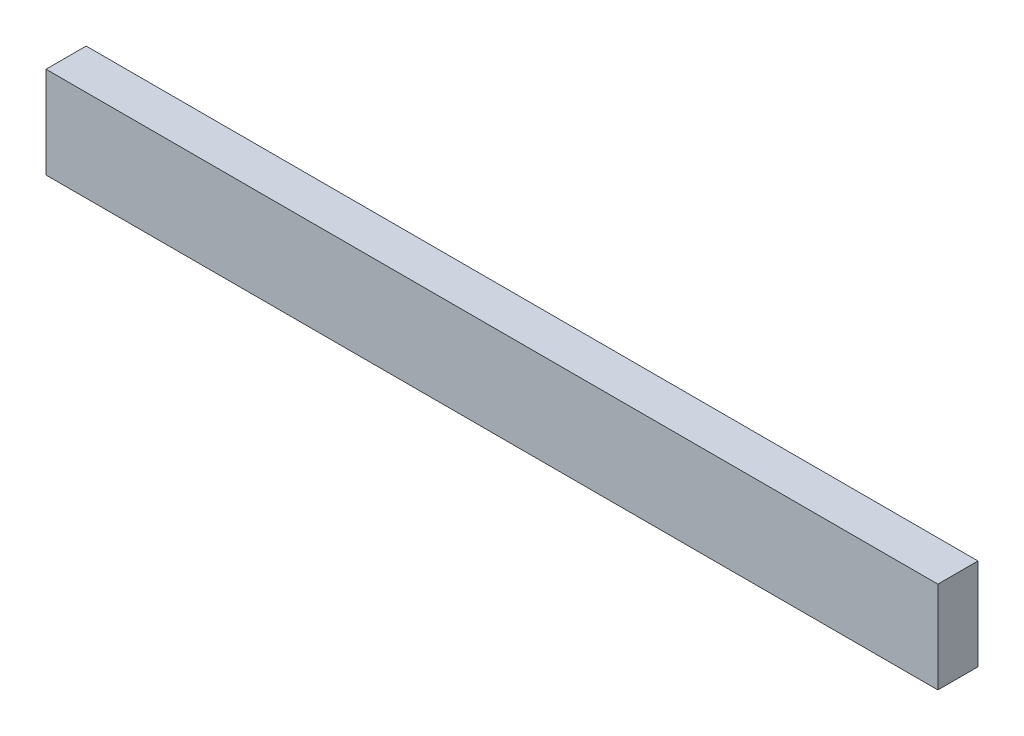
SolidWorks part; units mm, degrees
ref_plane "Front Plane" through (0, 0, 0) normal (0, 0, 1) x (1, 0, 0)
ref_plane "Top Plane" through (0, 0, 0) normal (0, 1, 0) x (1, 0, 0)
ref_plane "Right Plane" through (0, 0, 0) normal (1, 0, 0) x (0, 0, -1)
sketch "Sketch1" plane through (0, 0, 0) normal (0, 0, 1) x (1, 0, 0)
  line L1 (0, 0) -> (-400, 0)
  line L2 (0, 0) -> (0, 41.1073)
  line L3 (0, 41.1073) -> (-400, 41.1073)
  line L4 (-400, 0) -> (-400, 41.1073)
  dimension "D1" = 41.1073
  dimension "D2" = 400
extrude "Boss-Extrude1" add sketch "Sketch1" along normal blind 18
sketch "Sketch2" plane through (0, 41.1073, 0) normal (0, 1, 0) x (1, 0, 0)
  line L0 (-400, -18) -> (-400, 0) construction
  line L1 (0, -18) -> (-400, -18) construction
  point P0 (-390, -8)
  dimension "D1" = 10
  dimension "D2" = 10
ref_axis "Axis1" through (-390, 41.1073, 8) along (0, 1, 0)
sketch "Sketch3" plane through (0, 41.1073, 0) normal (0, 1, 0) x (1, 0, 0)
  line L0 (0, -11.15) -> (-2.5742, 0)
  line L1 (0, -18) -> (0, 0) construction
  line L2 (0, -18) -> (-400, -18) construction
  line L3 (0, 0) -> (-400, 0) construction
  line L4 (-2.5742, 0) -> (0, 0)
  line L5 (0, 0) -> (0, -11.15)
  dimension "D1" = 6.85
  dimension "D2" = 13
extrude "Cut-Extrude1" [suppressed] cut sketch "Sketch3" against normal through all
fillet "Fillet1" [suppressed] radius 10
